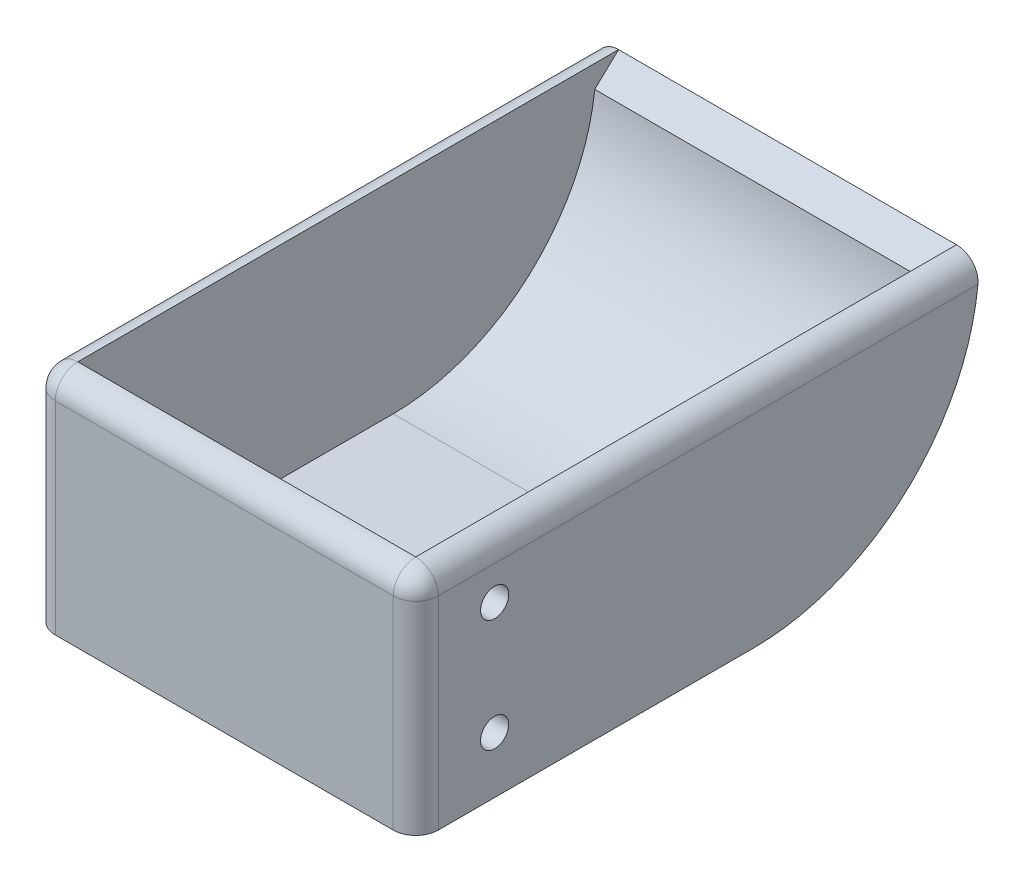
SolidWorks part; units mm, degrees
ref_plane "Front Plane" through (0, 0, 0) normal (0, 0, 1) x (1, 0, 0)
ref_plane "Top Plane" through (0, 0, 0) normal (0, 1, 0) x (1, 0, 0)
ref_plane "Right Plane" through (0, 0, 0) normal (1, 0, 0) x (0, 0, -1)
sketch "Sketch1" plane through (0, 0, 0) normal (1, 0, 0) x (0, 0, -1)
  line L0 (-60.96, 0) -> (-63.5, 0)
  line L1 (-63.5, 0) -> (-63.5, -25.4)
  line L2 (-63.5, -25.4) -> (-25.4, -25.4)
  line L3 (-60.96, 0) -> (-60.96, -22.86)
  line L5 (-60.96, -22.86) -> (-25.4, -22.86)
  line L6 (-2.6815, -2.54) -> (0, 0)
  line L8 (0, 0) -> (-63.5, 0) construction
  line L9 (-2.6815, -2.54) -> (-60.96, -2.54) construction
  line L10 (-60.96, -2.54) -> (-60.96, -22.86) construction
  arc A0 (-25.4, -25.4) -> (0, 0) centre (-25.4, 0) ccw
  arc A1 (-25.4, -22.86) -> (-2.6815, -2.54) centre (-25.4, 0) ccw
  dimension "D1" = 63.5
  dimension "D2" = 25.4
  dimension "D3" = 2.54
extrude "Boss-Extrude2" add sketch "Sketch1" along normal blind 38.1
sketch "Sketch2" plane through (38.1, 0, 0) normal (1, 0, 0) x (0, 0, -1)
  line L0 (-63.5, 0) -> (0, 0)
  line L1 (-63.5, 0) -> (-63.5, -25.4)
  line L2 (-63.5, -25.4) -> (-25.4, -25.4)
  arc A0 (-25.4, -25.4) -> (0, 0) centre (-25.4, 0) ccw
extrude "Boss-Extrude3" add sketch "Sketch2" along normal blind 2.54
sketch "Sketch3" plane through (0, 0, 0) normal (-1, 0, 0) x (0, 0, 1)
  line L0 (0, 0) -> (63.5, 0)
  line L1 (63.5, 0) -> (63.5, -25.4)
  line L2 (63.5, 0) -> (63.5, -25.4) construction
  line L3 (63.5, -25.4) -> (25.4, -25.4)
  arc A0 (25.4, -25.4) -> (0, 0) centre (25.4, 0) cw
  arc M1 (0, 0) -> (25.4, -25.4) centre (25.4, 0) ccw
  line M2 (25.4, -25.4) -> (63.5, -25.4)
  line M3 (63.5, -25.4) -> (63.5, 0)
  line M4 (63.5, 0) -> (60.96, 0)
  line M5 (60.96, 0) -> (60.96, -22.86)
  line M6 (60.96, -22.86) -> (25.4, -22.86)
  arc M7 (25.4, -22.86) -> (2.6815, -2.54) centre (25.4, 0) cw
  line M8 (2.6815, -2.54) -> (0, 0)
extrude "Boss-Extrude5" add sketch "Sketch3" along normal blind 2.54 contours M8 M1 M2 M3 M4 M5 M6 M7 | L0 M8 M7 M6 M5 region at (0, -1.7665, 0.8705) region at (0, -10.8244, 33.8765)
fillet "Fillet1" radius 2.54 1 edges at (40.64, 0, 31.75)
fillet "Fillet3" radius 2.54 1 edges at (-2.54, 0, 31.75)
fillet "Fillet5" radius 2.54 5 edges at (40.64, -13.97, 63.5) (39.8961, -0.7439, 63.5) (-2.54, -13.97, 63.5) (-1.7961, -0.7439, 63.5) (19.05, 0, 63.5)
ref_plane "Plane1" through (40.64, 0, 0) normal (1, 0, 0) x (0, 0, -1)
sketch "Sketch5" plane through (40.64, 0, 0) normal (1, 0, 0) x (0, 0, -1)
  line L0 (-60.96, -25.4) -> (-25.4, -25.4) construction
  line L2 (0, 0) -> (-60.96, 0) construction
  line L3 (-60.96, -2.54) -> (-60.96, -25.4) construction
  circle A0 centre (-54.61, -6.35) radius 1.5875
  circle A1 centre (-54.61, -19.05) radius 1.5875
  dimension "D5" = 3.175
  dimension "D6" = 3.175
  dimension "D1" = 6.35
  dimension "D2" = 6.35
  dimension "D3" = 6.35
  dimension "D4" = 6.35
extrude "Cut-Extrude1" cut sketch "Sketch5" against normal blind 2.54
